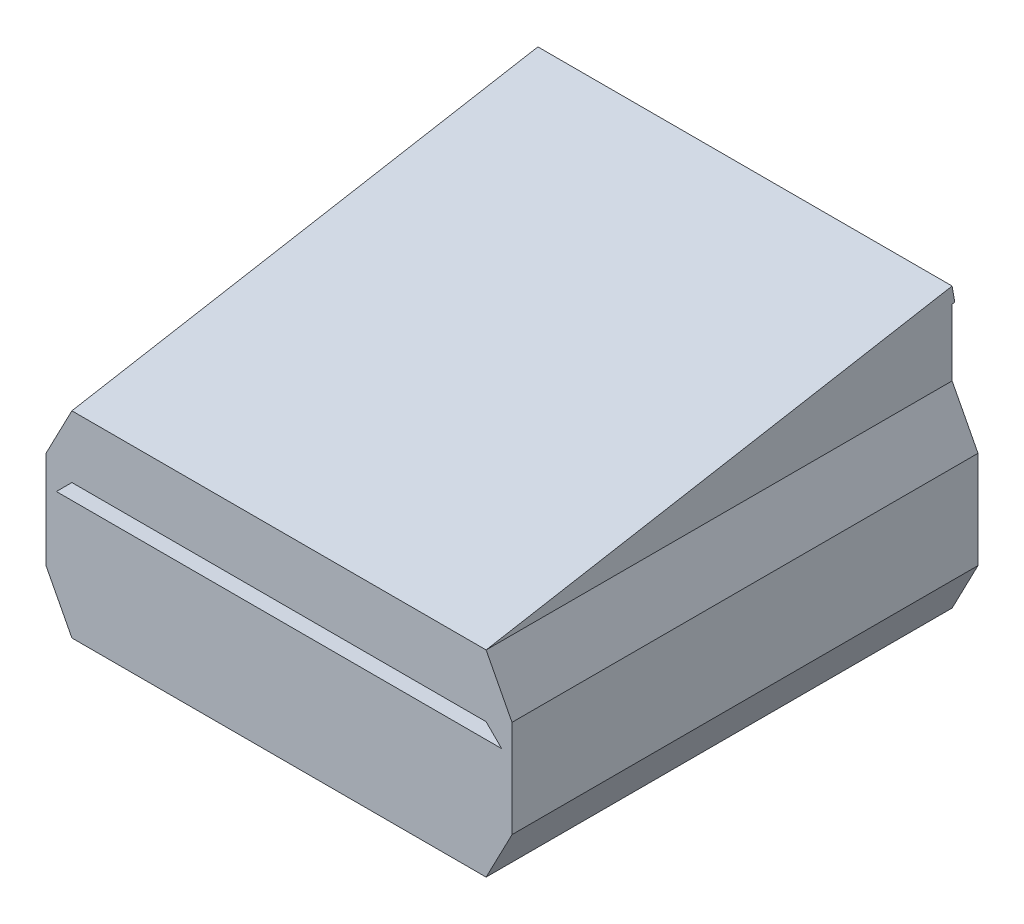
SolidWorks part; units mm, degrees
ref_plane "Front Plane" through (0, 0, 0) normal (0, 0, 1) x (1, 0, 0)
ref_plane "Top Plane" through (0, 0, 0) normal (0, 1, 0) x (1, 0, 0)
ref_plane "Right Plane" through (0, 0, 0) normal (1, 0, 0) x (0, 0, -1)
sketch "Sketch1" plane through (0, 0, 0) normal (0, 1, 0) x (1, 0, 0)
  line L1 (0, 0) -> (80, 0)
  line L2 (0, 0) -> (0, 90)
  line L3 (0, 90) -> (80, 90)
  line L4 (80, 0) -> (80, 90)
  dimension "D1" = 80
  dimension "D2" = 90
extrude "Boss-Extrude1 (Base)" add sketch "Sketch1" along normal blind 3
sketch "Sketch4" plane through (0, 0, 0) normal (0, 0, 1) x (1, 0, 0)
  line L0 (-3, 23) -> (0, 26)
  line L1 (0, 26) -> (0, 23)
  line L2 (0, 23) -> (-3, 23)
  line L3 (0, 3) -> (80, 3) construction
  line L6 (0, 3) -> (0, 0) construction
  line L7 (40, 28.9013) -> (40, -8.4397) construction
  line L8 (80, 3) -> (80, 0) construction
  line L9 (80, 23) -> (83, 23)
  line L10 (80, 26) -> (80, 23)
  line L11 (83, 23) -> (80, 26)
  dimension "D1" = 20
  dimension "D2" = 3
  dimension "D3" = 3
  dimension "D4" = 40
sketch "Sketch5" plane through (0, 0, 0) normal (0, 0, 1) x (1, 0, 0)
  line L6 (40, -8.4397) -> (40, 28.9013) construction
  line L11 (-5, 28.3909) -> (0, 38)
  line L12 (0, 38) -> (0, 0)
  line L13 (0, 0) -> (-5, 9.6091)
  line L14 (-5, 9.6091) -> (-5, 28.3909)
  line L16 (0, 3) -> (80, 3) construction
  line L17 (85, 9.6091) -> (85, 28.3909)
  line L18 (80, 0) -> (85, 9.6091)
  line L19 (80, 38) -> (80, 0)
  line L20 (85, 28.3909) -> (80, 38)
  dimension "D1" = 5
  dimension "D2" = 35
extrude "Boss-Extrude4 (Side Walls)" add sketch "Sketch5" against normal through all
extrude "Cut-Extrude2 (Guide Holes)" cut sketch "Sketch4" against normal through all
sketch "Sketch15" plane through (0, 0, 0) normal (0, 0, 1) x (1, 0, 0)
  line L1 (0, 23) -> (80, 23)
  line L2 (0, 23) -> (0, 3)
  line L3 (0, 3) -> (80, 3)
  line L4 (80, 23) -> (80, 3)
extrude "Boss-Extrude9 (Rear Wall)" add sketch "Sketch15" against normal blind 3
sketch "Sketch17" plane through (0, 23, 0) normal (0, 1, 0) x (1, 0, 0)
  line L1 (80, 3) -> (0, 3)
  line L2 (80, 3) -> (80, 0)
  line L3 (80, 0) -> (0, 0)
  line L4 (0, 3) -> (0, 0)
extrude "Boss-Extrude1" add sketch "Sketch17" along normal blind 12 from offset 3
sketch "Sketch20" plane through (0, 3, 0) normal (0, 1, 0) x (1, 0, 0)
  line L0 (80, 90) -> (0, 90) construction
  line L1 (0, 3) -> (3, 3)
  line L2 (0, 3) -> (0, 90)
  line L3 (0, 90) -> (3, 90)
  line L4 (3, 3) -> (3, 90)
  line L5 (40, 90) -> (40, 70.8429) construction
  line L6 (80, 3) -> (0, 3) construction
  line L7 (0, 3) -> (0, 0) construction
  line L8 (77, 3) -> (77, 90)
  line L9 (80, 90) -> (77, 90)
  line L10 (80, 3) -> (80, 90)
  line L11 (80, 3) -> (77, 3)
  dimension "D1" = 3
extrude "Boss-Extrude2" add sketch "Sketch20" along normal blind 12 from offset 23
chamfer "Chamfer1" distance 3 angle 45 2 edges at (77, 26, -46.5) (3, 26, -46.5)
sketch "Sketch26" plane through (0, 38, 0) normal (0, 1, 0) x (1, 0, 0)
  line L0 (77, 90) -> (80, 90)
  line L1 (80, 90) -> (80, 0)
  line L2 (80, 0) -> (0, 0)
  line L3 (0, 0) -> (0, 90)
  line L4 (0, 90) -> (0, 0) construction
  line L5 (0, 90) -> (3, 90)
  line L6 (3, 90) -> (0, 90) construction
  line L7 (3, 90) -> (3, 3)
  line L8 (3, 3) -> (77, 3)
  line L9 (77, 3) -> (77, 90)
extrude "Boss-Extrude5" add sketch "Sketch26" along normal blind 30
chamfer "Chamfer2" distance 30 angle 80 1 edges at (40, 68, 0) first distance on face at (40, 24.5, 0)
sketch "Sketch27" plane through (0, 36.8542, 6.4984) normal (0, 0.9848, 0.1736) x (1, 0, 0)
  line L1 (80, 6.5986) -> (0, 6.5986)
  line L2 (80, 6.5986) -> (80, 97.987)
  line L3 (80, 97.987) -> (0, 97.987)
  line L4 (0, 6.5986) -> (0, 97.987)
extrude "Boss-Extrude6" add sketch "Sketch27" against normal blind 3
